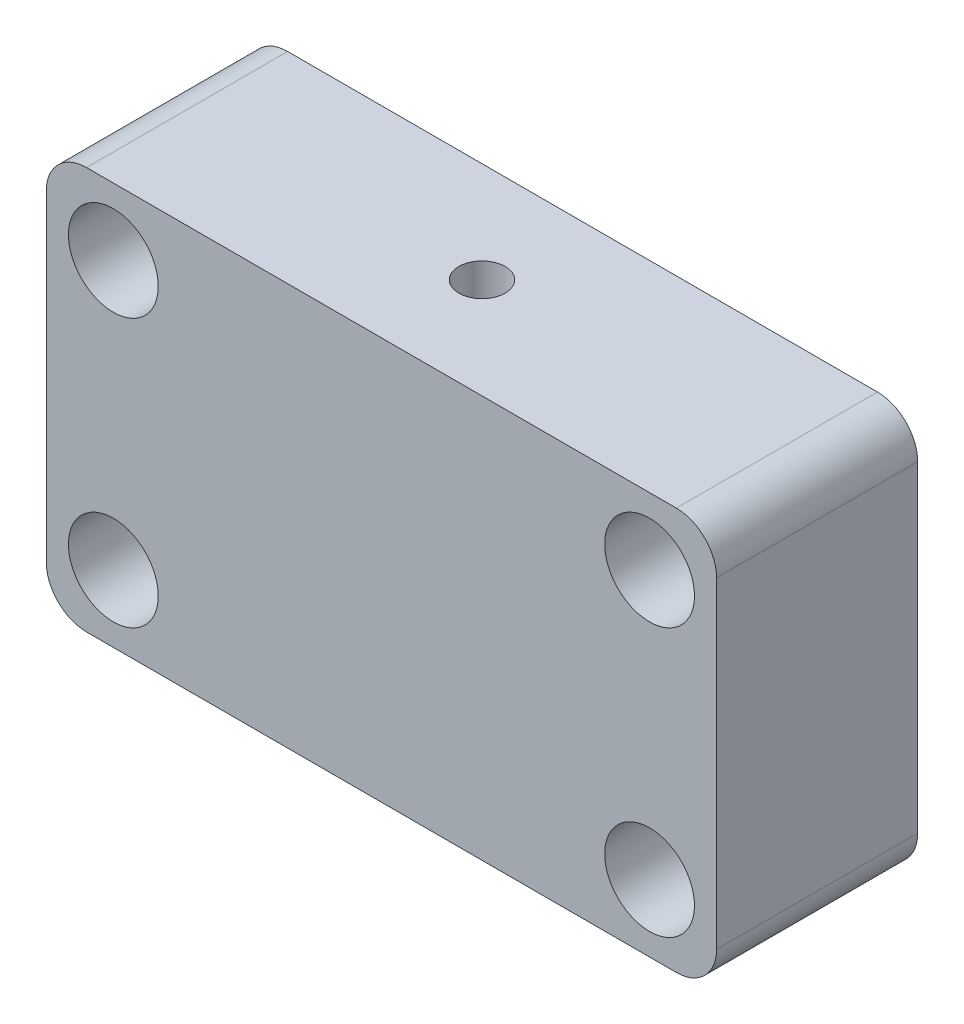
SolidWorks part; units mm, degrees
ref_plane "Front Plane" through (0, 0, 0) normal (0, 0, 1) x (1, 0, 0)
ref_plane "Top Plane" through (0, 0, 0) normal (0, 1, 0) x (1, 0, 0)
ref_plane "Right Plane" through (0, 0, 0) normal (1, 0, 0) x (0, 0, -1)
sketch "Sketch2" plane through (0, 0, 0) normal (0, 0, 1) x (1, 0, 0)
  line L1 (-25, -15) -> (25, -15)
  line L2 (-25, -15) -> (-25, 15)
  line L3 (-25, 15) -> (25, 15)
  line L4 (25, -15) -> (25, 15)
  line L5 (-25, -15) -> (25, 15) construction
  line L6 (-25, 15) -> (25, -15) construction
  circle A0 centre (20, 10) radius 3.35
  circle A1 centre (-20, 10) radius 3.35
  circle A2 centre (-20, -10) radius 3.35
  circle A3 centre (20, -10) radius 3.35
  point P0 (0, 0)
  dimension "D3" = 20
  dimension "D1" = 30
  dimension "D2" = 50
  dimension "D4" = 10
extrude "Boss-Extrude1" add sketch "Sketch2" along normal blind 15
sketch "Sketch7" plane through (0, 15, 0) normal (0, 1, 0) x (1, 0, 0)
  line L0 (0, 0) -> (0, -15) construction
  line L1 (25, 0) -> (-25, 0) construction
  line L2 (25, -15) -> (-25, -15) construction
  point P6 (0, -7.5)
sketch "Sketch8" plane through (0, 0, 0) normal (0, 0, -1) x (-1, 0, 0)
  line L0 (25, -15) -> (-25, 15) construction
  line L1 (25, 15) -> (-25, -15) construction
  point P4 (0, 0)
  point P8 (0, 0)
hole_wizard "#8-32 Tapped Hole1" positions "3DSketch1" profile "Sketch9" tap size "#8-32" standard "ANSI Inch"
sketch3d "3DSketch1"
  point P0 (0, 15, 7.5)
sketch "Sketch9" plane through (0, 15, 7.5) normal (1, 0, 0) x (0, 0, 1)
  line L0 (0, 0) -> (0, 6.0378)
  line L1 (0, 6.0378) -> (1.7272, 5)
  line L2 (1.7272, 5) -> (1.7272, 0)
  line L5 (1.7272, 0) -> (0, 0)
  line L10 (0, 6.0378) -> (-1.7272, 5) construction
  line L11 (0, -6.35) -> (0, 107.95) construction
  dimension "Tap Drill Dia." = 3.4544
  dimension "Tap Drill Depth" = 5
  dimension "Drill Angle" = 118
fillet "Fillet1" radius 3 1 edges at (25, 15, 7.5)
fillet "Fillet2" radius 3 1 edges at (-25, 15, 7.5)
fillet "Fillet3" radius 3 1 edges at (25, -15, 7.5)
fillet "Fillet4" radius 3 1 edges at (-25, -15, 7.5)
sketch "Sketch11" plane through (0, 0, 0) normal (0, 0, -1) x (-1, 0, 0)
  line L0 (-25, 0) -> (25, 0) construction
  line L1 (-25, -12) -> (-25, 12) construction
  line L2 (25, 12) -> (25, -12) construction
